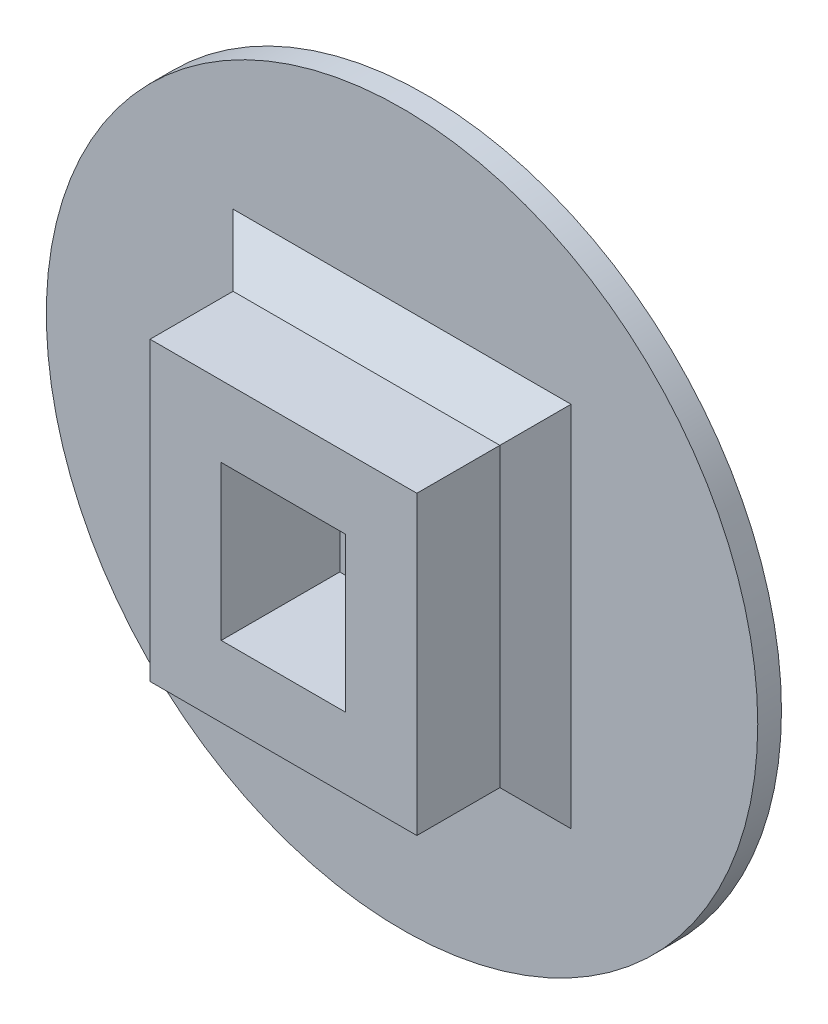
SolidWorks part; units mm, degrees
ref_plane "Plan de face" through (0, 0, 0) normal (0, 0, 1) x (1, 0, 0)
ref_plane "Plan de dessus" through (0, 0, 0) normal (0, 1, 0) x (1, 0, 0)
ref_plane "Plan de droite" through (0, 0, 0) normal (1, 0, 0) x (0, 0, -1)
sketch "Esquisse1" plane through (0, 0, 0) normal (0, 0, 1) x (1, 0, 0)
  circle A0 centre (0, 0) radius 6
  dimension "D1" = 12
extrude "Boss.-Extru.1" add sketch "Esquisse1" along normal blind 0.4
dome "Dôme1" faces to dome 1 distance 1.8 reverse direction no elliptical dome no face at (6, 0, 0) parameters "D1"=1.8
sketch "Esquisse3" plane through (0, 0, 0.4) normal (0, 0, 1) x (1, 0, 0)
  line L1 (-1.05, 1.3) -> (1.05, 1.3)
  line L2 (-1.05, 1.3) -> (-1.05, -1.3)
  line L3 (-1.05, -1.3) -> (1.05, -1.3)
  line L4 (1.05, 1.3) -> (1.05, -1.3)
  line L5 (-1.05, 1.3) -> (1.05, -1.3) construction
  line L6 (-1.05, -1.3) -> (1.05, 1.3) construction
  point P0 (0, 0)
  dimension "D1" = 2.1
  dimension "D2" = 2.6
extrude "Extru.-Mince1" add sketch "Esquisse3" along normal blind 2 thin thin type one direction wall 1.2
chamfer "Chanfrein1" distance 0.6 angle 45 4 edges at (0, -2.5, 0.4) (-2.25, 0, 0.4) (2.25, 0, 0.4) (0, 2.5, 0.4)
